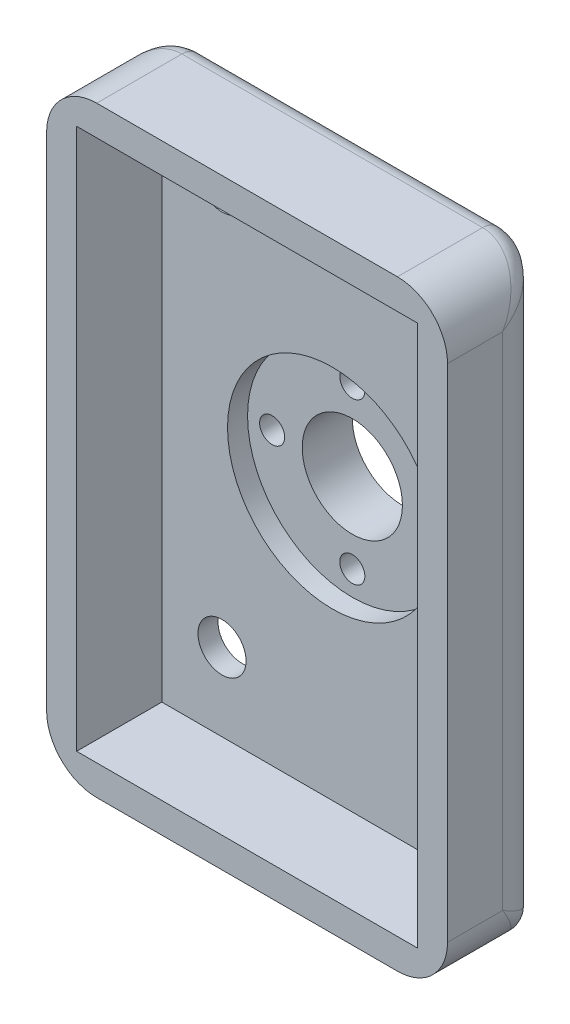
SolidWorks part; units mm, degrees
ref_plane "Front Plane" through (0, 0, 0) normal (0, 0, 1) x (1, 0, 0)
ref_plane "Top Plane" through (0, 0, 0) normal (0, 1, 0) x (1, 0, 0)
ref_plane "Right Plane" through (0, 0, 0) normal (1, 0, 0) x (0, 0, -1)
sketch "Sketch1" plane through (0, 0, 0) normal (0, 0, 1) x (1, 0, 0)
  line L0 (0, -11.559) -> (0, -10.441) construction
  circle A0 centre (0, -3) radius 1.25
  circle A1 centre (-8, -11) radius 1.25
  circle A2 centre (0, -19) radius 1.25
  circle A3 centre (8, -11) radius 1.25
  circle A4 centre (0, -11) radius 10.45
  spline S0 degree 3 poles (0.1424, -11.5375) (0.0489, -11.5664) (-0.0489, -11.5664) (-0.1424, -11.5375) knots 5.98544 5.98544 5.98544 5.98544 6.580931 6.580931 6.580931 6.580931 weights 1 0.970667 0.970667 1 construction
  spline S1 degree 3 poles (-0.1424, -10.4625) (-0.0489, -10.4336) (0.0489, -10.4336) (0.1424, -10.4625) knots 5.98544 5.98544 5.98544 5.98544 6.580931 6.580931 6.580931 6.580931 weights 1 0.970667 0.970667 1 construction
extrude "Boss-Extrude1" add sketch "Sketch1" along normal blind 5
sketch "Sketch2" plane through (0, 0, 5) normal (0, 0, 1) x (1, 0, 0)
  line L0 (0, -0.55) -> (0, -11) construction
  line L2 (-20, 19) -> (20, 19)
  line L3 (-20, 19) -> (-20, -41)
  line L4 (-20, -41) -> (20, -41)
  line L5 (20, 19) -> (20, -41)
  line L6 (-20, 19) -> (20, -41) construction
  line L7 (-20, -41) -> (20, 19) construction
  circle A0 centre (0, -11) radius 10.45 construction
  circle A2 centre (0, -3) radius 1.25 construction
  circle A3 centre (0, -3) radius 1.25
  circle A4 centre (-8, -11) radius 1.25 construction
  circle A5 centre (-8, -11) radius 1.25
  circle A6 centre (0, -19) radius 1.25 construction
  circle A7 centre (0, -19) radius 1.25
  circle A8 centre (8, -11) radius 1.25 construction
  circle A9 centre (8, -11) radius 1.25
  dimension "D1" = 40
  dimension "D2" = 60
extrude "Boss-Extrude3" add sketch "Sketch2" along normal blind 2
fillet "Fillet1" radius 2 2 edges at (0, -41, 5) (0, 19, 5)
sketch "Sketch3" plane through (0, 0, 7) normal (0, 0, 1) x (1, 0, 0)
  circle A0 centre (0, -11) radius 10.45 construction
  circle A1 centre (0, -11) radius 10.45
extrude "Cut-Extrude1" cut sketch "Sketch3" against normal blind 2
sketch "Sketch4" plane through (0, 0, 5) normal (0, 0, -1) x (-1, 0, 0)
  line L0 (20, -11) -> (0, -11) construction
  line L1 (20, 19) -> (20, -41) construction
  line L2 (0, -11) -> (0, 9.741) construction
  line L3 (0, 9.741) -> (-11, 9.741) construction
  arc A5 (-13.4, 9.741) -> (-8.6, 9.741) centre (-11, 9.741) ccw construction
  circle A16 centre (-11, 9.741) radius 2.4
  circle A17 centre (11, 9.741) radius 2.4
  dimension "D1" = 11
  dimension "D2" = 4.8
extrude "Cut-Extrude2" cut sketch "Sketch4" against normal blind 2
sketch "Sketch6" plane through (0, 0, 7) normal (0, 0, 1) x (1, 0, 0)
  line L0 (-11, 9.741) -> (-11, -30.259) construction
  line L1 (0, 0) -> (0, 19) construction
  line L2 (20, 19) -> (-20, 19) construction
  circle A0 centre (-11, -30.259) radius 2.4
  circle A1 centre (11, -30.259) radius 2.4
extrude "Cut-Extrude3" cut sketch "Sketch6" against normal blind 10
sketch "Sketch7" plane through (0, 0, 7) normal (0, 0, 1) x (1, 0, 0)
  line L0 (20, 19) -> (-20, 19) construction
  line L1 (20, 19) -> (-20, 19)
  line L2 (-20, 19) -> (-20, -41) construction
  line L3 (-20, 19) -> (-20, -41)
  line L4 (-20, -41) -> (20, -41) construction
  line L5 (-20, -41) -> (20, -41)
  line L6 (20, -41) -> (20, 19) construction
  line L7 (20, -41) -> (20, 19)
  line L8 (17, 16) -> (-17, 16)
  line L9 (-17, 16) -> (-17, -38)
  line L10 (-17, -38) -> (17, -38)
  line L11 (17, -38) -> (17, 16)
  dimension "D1" = 3
extrude "Boss-Extrude5" add sketch "Sketch7" along normal up to surface (8.5 mm away)
fillet "Fillet2" radius 5 10 edges at (-20, -41, 11.25) (-20, -40.4142, 5.5858) (-20, -11, 5) (-20, 18.4142, 5.5858) (20, -41, 11.25) (20, -40.4142, 5.5858) (20, -11, 5) (20, 18.4142, 5.5858) (-20, 19, 11.25) (20, 19, 11.25)
sketch "Sketch8" plane through (0, 0, 5) normal (0, 0, 1) x (1, 0, 0)
  circle A0 centre (0, -11) radius 5
  dimension "D1" = 10
extrude "Cut-Extrude4" cut sketch "Sketch8" against normal blind 10
